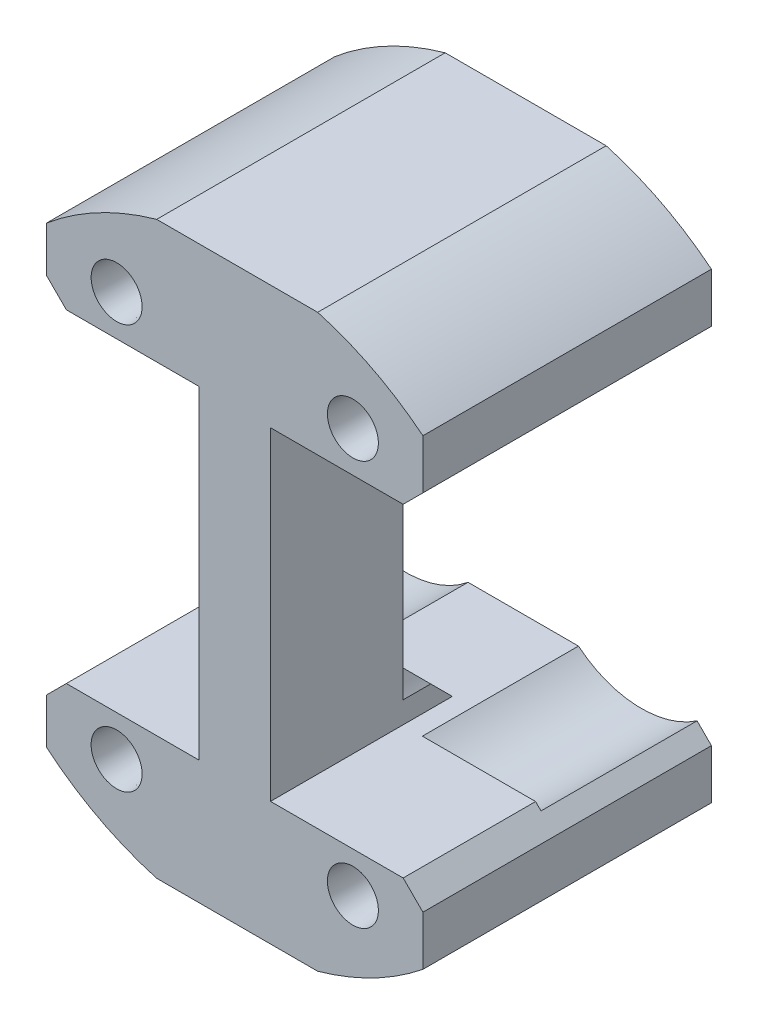
SolidWorks part; units mm, degrees
material "PET"
ref_plane "Front Plane" through (0, 0, 0) normal (0, 0, 1) x (1, 0, 0)
ref_plane "Top Plane" through (0, 0, 0) normal (0, 1, 0) x (1, 0, 0)
ref_plane "Right Plane" through (0, 0, 0) normal (1, 0, 0) x (0, 0, -1)
sketch "Sketch1" plane through (0, 0, 0) normal (0, 0, 1) x (1, 0, 0)
  line L0 (-3.2474, -10) -> (-12.2474, -10) construction
  line L1 (-12.2474, -10.3969) -> (11.935, -10.3969)
  line L2 (-12.2474, -10.3969) -> (-12.2474, -18.3344)
  line L3 (-12.2474, -18.3344) -> (11.935, -18.3344)
  line L4 (11.935, -10.3969) -> (11.935, -18.3344)
  line L6 (-12.2474, -10) -> (-12.2474, -12.5) construction
  line L8 (11.935, -12.5) -> (11.935, -10) construction
  dimension "D1" = 0.3969
  dimension "D2" = 7.9375
extrude "Boss-Extrude1" add sketch "Sketch1" along normal up to surface (18.5375 mm away)
sketch "Sketch8" plane through (0, 0, 0) normal (0, 0, -1) x (-1, 0, 0)
  line L0 (5.1723, -18.3344) -> (12.2474, -18.3344)
  line L4 (12.2474, -18.3344) -> (12.2474, -10.3969)
  line L5 (12.2474, -10.3969) -> (-11.935, -10.3969)
  line L6 (-11.935, -10.3969) -> (-11.935, -18.3344)
  line L7 (-11.935, -18.3344) -> (12.2474, -18.3344)
  line L8 (12.2474, -18.3344) -> (12.2474, -14.5912)
  line L10 (-11.935, -14.8478) -> (-11.935, -18.3344)
  line L11 (-11.935, -18.3344) -> (-5.1723, -18.3344)
  arc A0 (-17.3537, -7.8581) -> (17.3537, -7.8581) centre (0, 0) ccw construction
  arc A1 (-11.935, -14.8478) -> (-5.1723, -18.3344) centre (0, 0) ccw
  arc A2 (5.1723, -18.3344) -> (12.2474, -14.5912) centre (0, 0) ccw
  dimension "D1" = 0
extrude "Cut-Extrude2" cut sketch "Sketch8" against normal through all
ref_plane "Plane1" through (0, 0, 0) normal (0, -1, 0) x (-1, 0, 0)
mirror "Mirror2" about plane through (0, 0, 0) normal (0, -1, 0) of bodies 106 102
sketch "Sketch3" plane through (0, 0, 18.5375) normal (0, 0, 1) x (1, 0, 0)
  line L0 (-0.1562, 10.3969) -> (-0.1562, -10.3969) construction
  line L1 (-12.2474, 10.3969) -> (11.935, 10.3969) construction
  line L2 (-12.2474, -10.3969) -> (11.935, -10.3969) construction
  line L3 (-3.2474, 10) -> (-3.2474, -10) construction
  line L4 (2.1413, -10.3969) -> (-2.4537, -10.3969)
  line L5 (2.1413, -10.3969) -> (2.1413, 10.3969)
  line L6 (2.1413, 10.3969) -> (-2.4537, 10.3969)
  line L7 (-2.4537, -10.3969) -> (-2.4537, 10.3969)
  line L8 (2.1413, -10.3969) -> (-2.4537, 10.3969) construction
  line L9 (2.1413, 10.3969) -> (-2.4537, -10.3969) construction
  point P6 (-0.1562, 0)
  dimension "D1" = 0.7937
extrude "Boss-Extrude2" add sketch "Sketch3" against normal blind 8.509
chamfer "Chamfer2" distance 3.175 angle 45 2 edges at (-0.1562, 10.3969, 10.0285) (-0.1562, -10.3969, 10.0285)
chamfer "Chamfer4" distance 1.27 angle 45 4 edges at (-12.2474, -10.3969, 9.2688) (-12.2474, 10.3969, 9.2688) (11.935, 10.3969, 9.2688) (11.935, -10.3969, 9.2688)
sketch "Sketch2" plane through (0, 0, 0) normal (0, 0, -1) x (-1, 0, 0)
  line L0 (-28.4114, 0) -> (28.4114, 0) construction
  arc A0 (4.5737, 0) -> (10.9211, 0) centre (7.7474, -5.5) ccw
  arc A1 (-10.6088, 0) -> (-4.2613, 0) centre (-7.435, -5.5) ccw
  arc A2 (4.5737, 0) -> (10.9211, 0) centre (7.7474, 5.5) cw
  arc A3 (-10.6088, 0) -> (-4.2613, 0) centre (-7.435, 5.5) cw
  dimension "D1" = 12.7
extrude "Cut-Extrude1" cut sketch "Sketch2" against normal up to surface (10.0285 mm away) up to face at (-0.1562, 0, 10.0285)
hole_wizard "Hole1" positions "Sketch4" profile "Sketch5" legacy
sketch "Sketch4" plane through (0, 0, 18.5375) normal (0, 0, 1) x (1, 0, 0)
  point P0 (-7.7474, 13)
  point P3 (7.435, 13)
  point P6 (7.435, -13)
  point P9 (-7.7474, -13)
sketch "Sketch5" plane through (-7.7474, 13, 18.5375) normal (1, 0, 0) x (0, -1, 0)
  line L0 (0, 0) -> (0, 2.921)
  line L1 (0, 2.921) -> (1.4986, 2.921)
  line L2 (1.4986, 2.921) -> (1.6383, 0)
  line L3 (1.6383, 0) -> (0, 0)
  line L4 (0, 110) -> (0, -10) construction
  dimension "Minor Diameter" = 2.9972
  dimension "Depth" = 2.921
  dimension "Major Diameter" = 3.2766
hole_wizard "#0 Clearance Hole1" positions "Sketch10" profile "Sketch11" hole size "#0" standard "ANSI Inch"
sketch "Sketch10" plane through (0, 0, 18.5375) normal (0, 0, 1) x (1, 0, 0)
  point P0 (7.435, 13)
  point P3 (7.435, -13)
  point P6 (-7.7474, -13)
  point P9 (-7.7474, 13)
sketch "Sketch11" plane through (7.435, 13, 18.5375) normal (1, 0, 0) x (0, -1, 0)
  line L0 (0, 0) -> (0, 6.9071)
  line L1 (0, 6.9071) -> (0.9271, 6.35)
  line L2 (0.9271, 6.35) -> (0.9271, 0)
  line L5 (0.9271, 0) -> (0, 0)
  line L10 (0, 6.9071) -> (-0.9271, 6.35) construction
  line L11 (0, -6.35) -> (0, 107.95) construction
  dimension "Hole Dia." = 1.8542
  dimension "Hole Depth" = 6.35
  dimension "Drill Angle" = 118
hole_wizard "Hole2" positions "3DSketch1" profile "Sketch9" legacy
sketch3d "3DSketch1"
  line L0 (7.435, -11.85, 0) -> (7.435, -17.5392, 0) construction
  line L2 (-7.7474, -11.85, 0) -> (-7.7474, -17.4034, 0) construction
  line L4 (0, 0, 0) -> (-12.2474, 0, 0) construction
  line L6 (-12.2474, 11.6669, 0) -> (-12.2474, 14.5912, 0) construction
  line L7 (7.435, 11.85, 0) -> (7.435, 17.5392, 0) construction
  line L9 (-7.7474, 11.85, 0) -> (-7.7474, 17.4034, 0) construction
  arc A0 (11.0137, -10.7455, 0) -> (3.3924, -10.3969, 0) centre (7.435, -5.5, 0) ccw construction
  arc A1 (5.1723, -18.3344, 0) -> (11.935, -14.8478, 0) centre (0, 0, 0) ccw construction
  arc A2 (-3.7048, -10.3969, 0) -> (-11.3261, -10.7455, 0) centre (-7.7474, -5.5, 0) ccw construction
  arc A3 (-12.2474, -14.5912, 0) -> (-5.1723, -18.3344, 0) centre (0, 0, 0) ccw construction
  arc A4 (3.3924, 10.3969, 0) -> (11.0137, 10.7455, 0) centre (7.435, 5.5, 0) ccw construction
  arc A5 (5.1723, 18.3344, 0) -> (11.935, 14.8478, 0) centre (0, 0, 0) ccw construction
  arc A6 (-11.3261, 10.7455, 0) -> (-3.7048, 10.3969, 0) centre (-7.7474, 5.5, 0) ccw construction
  arc A7 (-12.2474, 14.5912, 0) -> (-5.1723, 18.3344, 0) centre (0, 0, 0) ccw construction
  point P4 (7.435, -14.6946, 0)
  point P6 (-7.7474, -14.6946, 0)
  point P15 (7.435, -5.5, -6.35)
  point P19 (0, 0, 19.05)
  point P27 (-7.7474, -5.5, -6.35)
  point P31 (0, 0, 19.05)
  point P44 (7.435, 14.6946, 0)
  point P46 (-7.7474, 14.6946, 0)
  point P54 (7.435, 5.5, -6.35)
  point P58 (0, 0, -19.05)
  point P65 (-7.7474, 5.5, -6.35)
  point P69 (0, 0, -19.05)
  point P71 (7.435, 13.296, 0)
  point P72 (7.435, 14.6946, 0)
  point P73 (-7.7474, 14.6946, 0)
  point P74 (0, 0, 0)
  point P75 (7.435, -14.6946, 0)
  point P76 (-7.7474, -14.6946, 0)
sketch "Sketch9" plane through (7.435, -14.6946, 0) normal (1, 0, 0) x (0, 1, 0)
  line L0 (0, 0) -> (0, 2.921)
  line L1 (0, 2.921) -> (1.4986, 2.921)
  line L2 (1.4986, 2.921) -> (1.6383, 0)
  line L3 (1.6383, 0) -> (0, 0)
  line L4 (0, 110) -> (0, -10) construction
  dimension "Minor Diameter" = 2.9972
  dimension "Depth" = 2.921
  dimension "Major Diameter" = 3.2766
hole_wizard "#0 Clearance Hole2" positions "Sketch12" profile "Sketch13" hole size "#0" standard "ANSI Inch"
sketch "Sketch12" plane through (0, 0, 0) normal (0, 0, -1) x (-1, 0, 0)
  point P0 (-7.435, -14.6946)
  point P3 (-7.435, 14.6946)
  point P6 (7.7474, 14.6946)
  point P9 (7.7474, -14.6946)
sketch "Sketch13" plane through (7.435, -14.6946, 0) normal (1, 0, 0) x (0, 1, 0)
  line L0 (0, 0) -> (0, 6.9071)
  line L1 (0, 6.9071) -> (0.9271, 6.35)
  line L2 (0.9271, 6.35) -> (0.9271, 0)
  line L5 (0.9271, 0) -> (0, 0)
  line L10 (0, 6.9071) -> (-0.9271, 6.35) construction
  line L11 (0, -6.35) -> (0, 107.95) construction
  dimension "Hole Dia." = 1.8542
  dimension "Hole Depth" = 6.35
  dimension "Drill Angle" = 118
